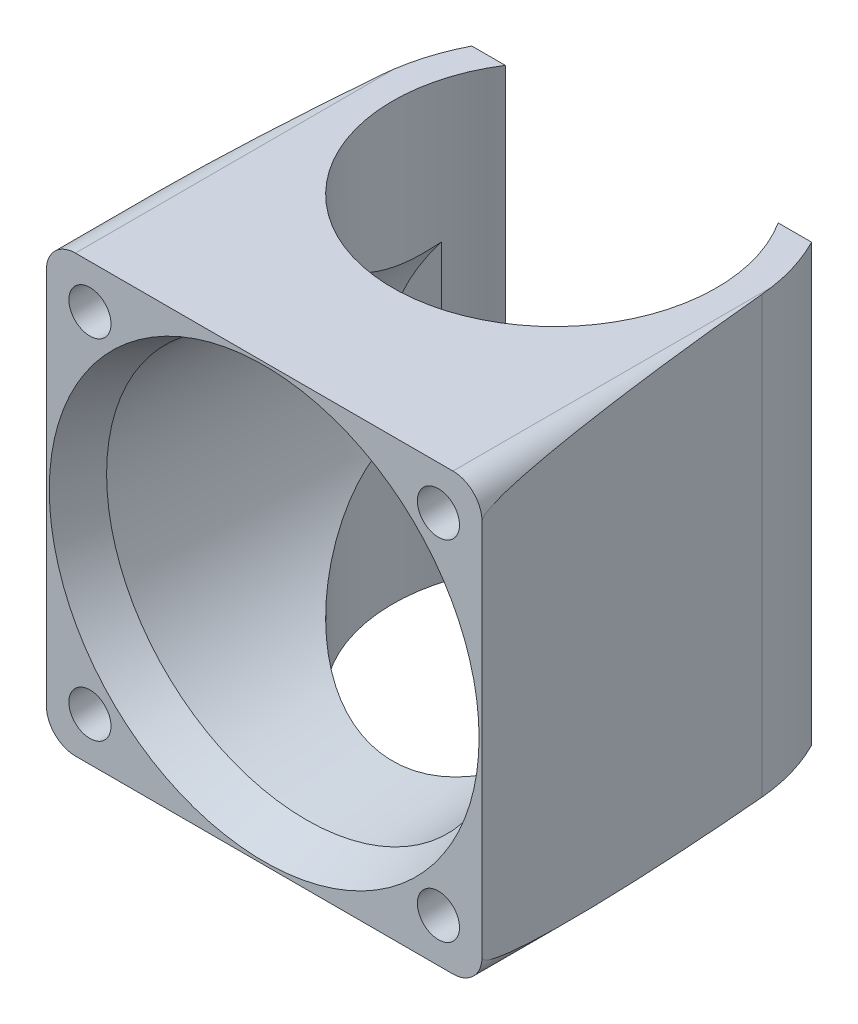
SolidWorks part; units mm, degrees
ref_plane "Alzado" through (0, 0, 0) normal (0, 0, 1) x (1, 0, 0)
ref_plane "Planta" through (0, 0, 0) normal (0, 1, 0) x (1, 0, 0)
ref_plane "Vista lateral" through (0, 0, 0) normal (1, 0, 0) x (0, 0, -1)
sketch "Croquis1" plane through (0, 0, 0) normal (0, 0, 1) x (1, 0, 0)
  line L1 (-15, -15) -> (15, -15)
  line L2 (-15, -15) -> (-15, 15)
  line L3 (-15, 15) -> (15, 15)
  line L4 (15, -15) -> (15, 15)
  line L5 (-15, -15) -> (15, 15) construction
  line L6 (-15, 15) -> (15, -15) construction
  point P0 (0, 0)
  dimension "D1" = 30
  dimension "D2" = 30
extrude "Saliente-Extruir1" add sketch "Croquis1" against normal blind 26
fillet "Redondeo1" radius 2 4 edges at (15, 15, -13) (15, -15, -13) (-15, -15, -13) (-15, 15, -13)
sketch "Croquis2" plane through (0, 0, 0) normal (0, 0, 1) x (1, 0, 0)
  line L1 (-12, -12) -> (12, -12) construction
  line L2 (-12, -12) -> (-12, 12) construction
  line L3 (-12, 12) -> (12, 12) construction
  line L4 (12, -12) -> (12, 12) construction
  line L5 (-12, -12) -> (12, 12) construction
  line L6 (-12, 12) -> (12, -12) construction
  circle A0 centre (-12, 12) radius 1.45
  circle A1 centre (12, 12) radius 1.45
  circle A2 centre (12, -12) radius 1.45
  circle A3 centre (-12, -12) radius 1.45
  point P0 (0, 0)
  dimension "D3" = 2.9
  dimension "D1" = 24
  dimension "D2" = 24
extrude "Cortar-Extruir1" cut sketch "Croquis2" against normal blind 5
sketch "Croquis3" plane through (0, 15, 0) normal (0, 1, 0) x (1, 0, 0)
  line L0 (13, 26) -> (-13, 26) construction
  line L1 (-15, 0) -> (-13.0972, 21.1768)
  line L2 (15, 0) -> (13.0972, 21.1768)
  line L3 (15, 0) -> (15, 26)
  line L4 (15, 26) -> (13, 26) construction
  line L5 (15, 26) -> (13, 26)
  line L6 (13, 26) -> (-13, 26)
  line L7 (-13, 26) -> (-15, 26) construction
  line L8 (-13, 26) -> (-15, 26)
  line L9 (-15, 0) -> (-15, 26)
  circle A0 centre (0, 20) radius 11.15
  circle A1 centre (0, 20) radius 13.15
  line M3 (13, 0) -> (13, 26)
  line M4 (13, 26) -> (-13, 26)
  line M5 (-13, 26) -> (-13, 0)
  dimension "D1" = 22.3
  dimension "D3" = 26.3
  dimension "D2" = 6
extrude "Cortar-Extruir2" cut sketch "Croquis3" against normal through all contours A1 L8 L9 L1 M5 | A1 L6 M5 | L6 A0 | A1 L2 L3 L5 M3 | A1 M3 M4 region at (-14.2491, 15, -17.1781) region at (-12.6014, 15, -24.8069) region at (0, 15, -18.2831) region at (12.6014, 15, -24.8069) region at (14.2491, 15, -17.1781)
sketch "Croquis5" plane through (0, 0, 0) normal (0, 0, 1) x (1, 0, 0)
  circle A0 centre (0, 0) radius 14
  dimension "D1" = 28
extrude "Cortar-Extruir3" cut sketch "Croquis5" against normal up to vertex (21.1768 mm away) draft 5 up to point (13.0972, 14.9976, -21.1768)
chamfer "Chaflán1" distance 2 angle 27 2 edges at (11.0877, 0, -21.1768) (-11.0877, 0, -21.1768) first distance on face at (0, 0, -17.425)
chamfer "Chaflán2" distance 0.8 angle 70 1 edges at (14, 0, 0) first distance on face at (14, 0, 0)
